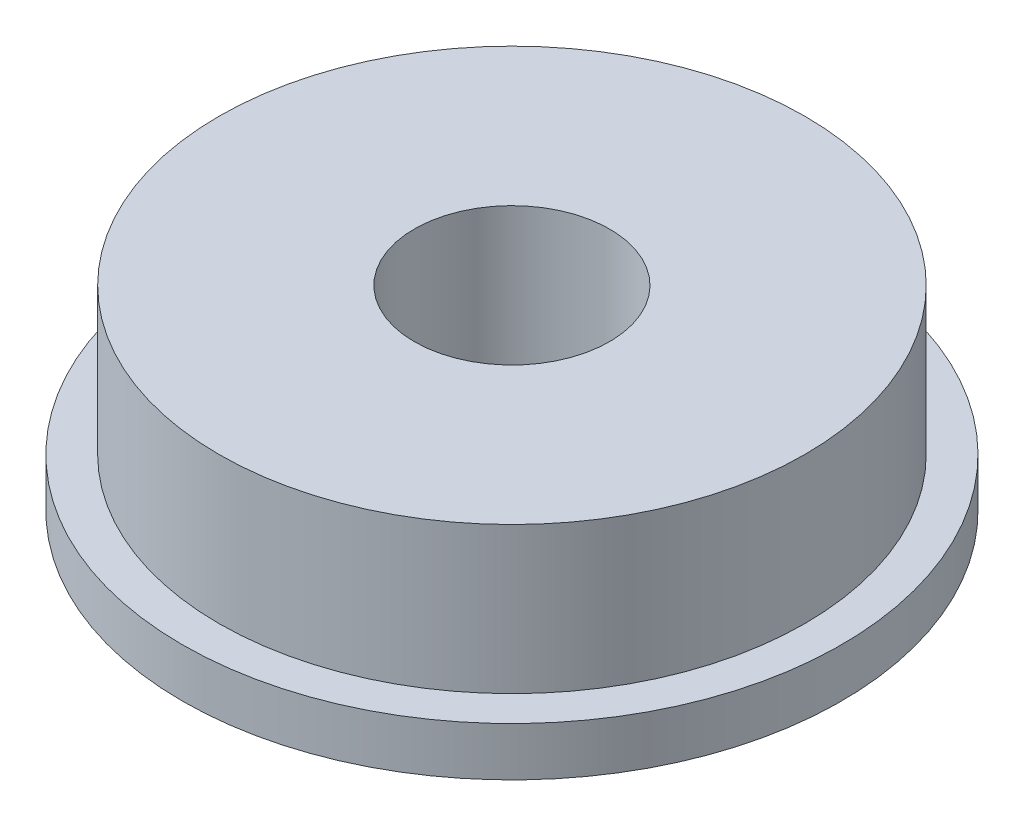
SolidWorks part; units mm, degrees
ref_plane "Front" through (0, 0, 0) normal (0, 0, 1) x (1, 0, 0)
ref_plane "Top" through (0, 0, 0) normal (0, 1, 0) x (1, 0, 0)
ref_plane "Right" through (0, 0, 0) normal (1, 0, 0) x (0, 0, -1)
sketch "Sketch1" plane through (0, 0, 0) normal (0, 1, 0) x (1, 0, 0)
  circle A0 centre (0, 0) radius 2
  circle A1 centre (0, 0) radius 6
  circle A2 centre (0, 0) radius 6.75
  dimension "D1" = 4
  dimension "D2" = 12
  dimension "D3" = 13.5
extrude "Boss-Extrude1" add sketch "Sketch1" along normal blind 4 contours A1 A0 region at (-5.8303, 0, 0)
extrude "Boss-Extrude2" add sketch "Sketch1<3>" along normal blind 1 contours A2 A1 region at (-6.5591, 0, 0)
sketch "Sketch1<3>" plane through (0, 0, 0) normal (0, 1, 0) x (1, 0, 0) same geometry as "Sketch1"
